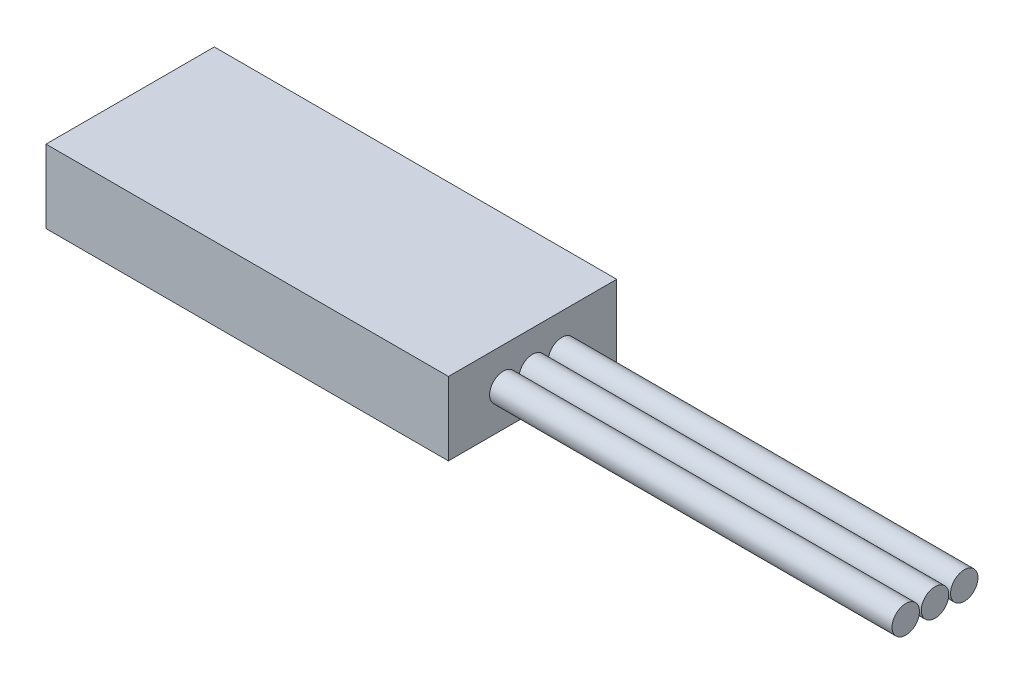
SolidWorks part; units mm, degrees
ref_plane "Front Plane" through (0, 0, 0) normal (0, 0, 1) x (1, 0, 0)
ref_plane "Top Plane" through (0, 0, 0) normal (0, 1, 0) x (1, 0, 0)
ref_plane "Right Plane" through (0, 0, 0) normal (1, 0, 0) x (0, 0, -1)
sketch "Sketch1" plane through (0, 0, 0) normal (1, 0, 0) x (0, 0, -1)
  line L1 (-4.6, -2) -> (4.6, -2)
  line L2 (-4.6, -2) -> (-4.6, 2)
  line L3 (-4.6, 2) -> (4.6, 2)
  line L4 (4.6, -2) -> (4.6, 2)
  line L5 (-4.6, -2) -> (4.6, 2) construction
  line L6 (-4.6, 2) -> (4.6, -2) construction
  point P0 (0, 0)
  dimension "D1" = 9.2
  dimension "D2" = 4
extrude "Boss-Extrude1" add sketch "Sketch1" along normal blind 22
shell "Shell1" thickness 0.5 removed face at (0, 0, 0)
sketch "Sketch2" plane through (22, 0, 0) normal (1, 0, 0) x (0, 0, -1)
  line L0 (0.85, 0) -> (0.75, 0) construction
  line L1 (-0.75, 0) -> (-0.85, 0) construction
  circle A0 centre (0, 0) radius 0.75
  circle A1 centre (-1.6, 0) radius 0.75
  circle A2 centre (1.6, 0) radius 0.75
  dimension "D1" = 1.5
  dimension "D2" = 0.1
ref_axis "Axis1" through (22, 0, 0) along (1, 0, 0)
ref_plane "Plane1" through (0, 0, 0) normal (0, 0.7071, 0.7071) x (1, 0, 0)
sketch "Sketch3" plane through (0, 0, 0) normal (0, 0.7071, 0.7071) x (1, 0, 0)
  line L0 (22, 0) -> (26.5, 0)
  line L1 (34.2913, 6.1846) -> (36.5605, 15.9238)
  arc A0 (34.2913, 6.1846) -> (26.5, 0) centre (26.5, 8) cw
  dimension "D1" = 4.5
  dimension "D2" = 8
  dimension "D4" = 10
sweep "Sweep1" [suppressed] add profiles "Sketch2" path "Sketch3" parameters "D4"=10
ref_plane "Plane2" [suppressed] through (19.5, 0, 0) normal (1, 0, 0) x (0, 0, -1)
mirror "Mirror1" [suppressed] about plane through (19.5, 0, 0) normal (1, 0, 0) of bodies 102
delete or keep bodies "Body-Delete/Keep 1" [suppressed] type delete bodies bodies 102
extrude "Boss-Extrude2" add sketch "Sketch2<2>" along normal blind 22
sketch "Sketch2<2>" plane through (22, 0, 0) normal (1, 0, 0) x (0, 0, -1) same geometry as "Sketch2"
other "Freeze***"
